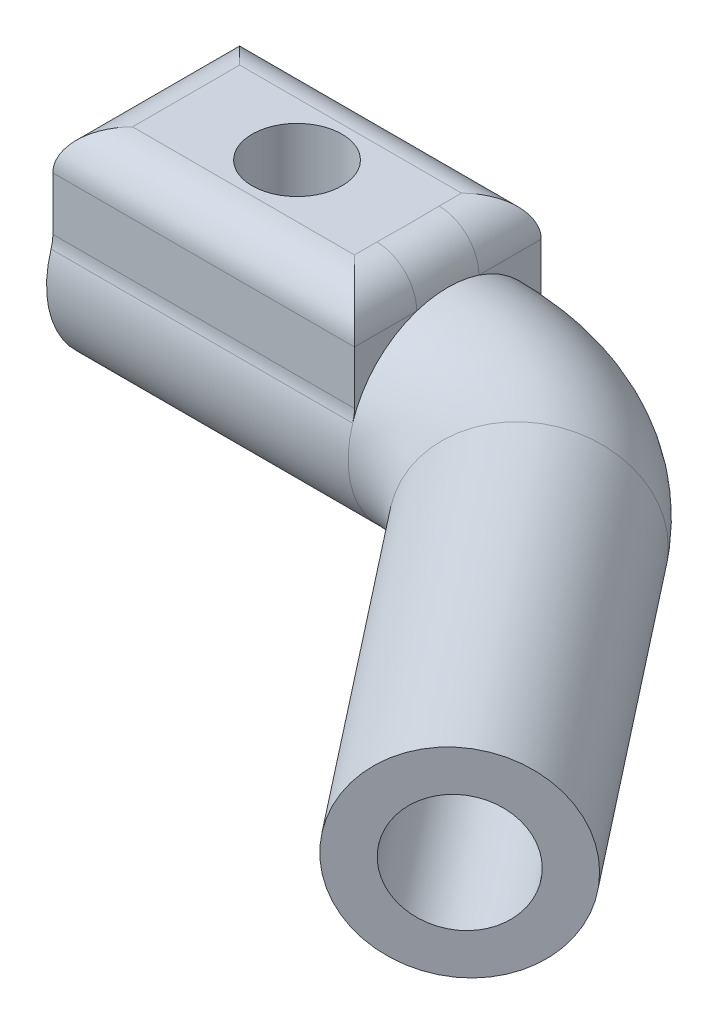
SolidWorks part; units mm, degrees
ref_plane "Front" through (0, 0, 0) normal (0, 0, 1) x (1, 0, 0)
ref_plane "Top" through (0, 0, 0) normal (0, 1, 0) x (1, 0, 0)
ref_plane "Right" through (0, 0, 0) normal (1, 0, 0) x (0, 0, -1)
sketch "Sketch1" plane through (0, 0, 0) normal (0, 1, 0) x (1, 0, 0)
  line L0 (0, 0) -> (15.1284, 0)
  line L1 (23.0028, -3.8361) -> (35.4097, -19.6861)
  line L2 (15.1284, 0) -> (20, 0) construction
  line L3 (23.0028, -3.8361) -> (20, 0) construction
  arc A0 (23.0028, -3.8361) -> (15.1284, 0) centre (15.1284, -10) ccw
  point P10 (20, 0)
  dimension "D1" = 10
  dimension "D2" = 128.053
  dimension "D3" = 20
  dimension "D4" = 25
sketch "Sketch2" plane through (0, 0, 0) normal (1, 0, 0) x (0, 0, -1)
  circle A1 centre (0, 0) radius 5
  dimension "D1" = 10
sweep "Sweep1" add profiles "Sketch2" path "Sketch1"
sketch "Sketch3" plane through (0, 0, 0) normal (0, 1, 0) x (1, 0, 0)
  line L1 (0, 0) -> (6.25, 0) construction
  line L2 (0, -5) -> (15.1284, -5) construction
  line L3 (12.5, 5) -> (0, 5)
  line L4 (12.5, 5) -> (12.5, -5)
  line L5 (12.5, -5) -> (0, -5)
  line L6 (0, 5) -> (0, -5)
  line L7 (12.5, 5) -> (0, -5) construction
  line L8 (12.5, -5) -> (0, 5) construction
  line L9 (0, 5) -> (0, -5) construction
  dimension "D1" = 12.5
extrude "Boss-Extrude1" [suppressed] add sketch "Sketch3" along normal blind 5
sketch "Sketch4" plane through (0, 0, 0) normal (-1, 0, 0) x (0, 0, 1)
  line L0 (-2.498, 1.75) -> (2.498, 1.75)
  circle A0 centre (0, 0) radius 3.05 construction
  arc A1 (-2.498, 1.75) -> (2.498, 1.75) centre (0, 0) ccw
  point P5 (0, -3.05)
  dimension "D1" = 6.1
  dimension "D2" = 4.8
extrude "Cut-Extrude1" cut sketch "Sketch4" against normal blind 12.5
sketch "Sketch5" plane through (23.0084, 0, 29.3935) normal (0.6164, 0, 0.7874) x (0.7874, 0, -0.6164)
  circle A0 centre (15.7489, 0) radius 2.95
  dimension "D1" = 5.9
sketch "Sketch6" [suppressed] plane through (0, 5, 0) normal (0, 1, 0) x (1, 0, 0)
  line L0 (0, 5) -> (12.5, -5) construction
  line L1 (0, -5) -> (12.5, 5) construction
  circle A0 centre (6.25, 0) radius 1.7
  point P8 (6.25, 0)
  dimension "D1" = 3.4
extrude "Cut-Extrude2" [suppressed] cut sketch "Sketch6" against normal up to next
extrude "Cut-Extrude3" cut sketch "Sketch5" against normal blind 10
fillet "Fillet1" [suppressed] radius 1
sketch "Sketch14" plane through (0, 1.75, 0) normal (0, -1, 0) x (1, 0, 0)
  line L6 (0, 5) -> (15.1284, 5)
  line L7 (0, 5) -> (0, -5)
  line L8 (0, -5) -> (15.1284, -5)
  line L9 (15.1284, 5) -> (15.1284, -5)
extrude "Cut-Extrude4" cut sketch "Sketch14" against normal blind 5
sketch "Sketch15" plane through (0, 1.75, 0) normal (0, 1, 0) x (1, 0, 0)
  line L1 (0, 4.6837) -> (15.1284, 4.6837)
  line L2 (0, 4.6837) -> (0, -4.6837)
  line L3 (0, -4.6837) -> (15.1284, -4.6837)
  line L4 (15.1284, 4.6837) -> (15.1284, -4.6837)
extrude "Boss-Extrude3" add sketch "Sketch15" along normal blind 5
fillet "Fillet2" radius 2 2 edges at (7.5642, 1.75, -4.6837) (7.5642, 1.75, 4.6837)
fillet "Fillet3" radius 2 4 edges at (7.5642, 6.75, -4.6837) (15.1284, 6.75, 0) (7.5642, 6.75, 4.6837) (0, 6.75, 0)
sketch "Sketch16" plane through (0, 6.75, 0) normal (0, 1, 0) x (1, 0, 0)
  line L0 (2, 2.6837) -> (13.1284, -2.6837) construction
  line L1 (2, -2.6837) -> (13.1284, 2.6837) construction
  line L2 (13.1284, 2.6837) -> (2, 2.6837) construction
  circle A0 centre (7.5642, 0) radius 2.25
  dimension "D1" = 4.5
extrude "Cut-Extrude5" cut sketch "Sketch16" against normal up to next
